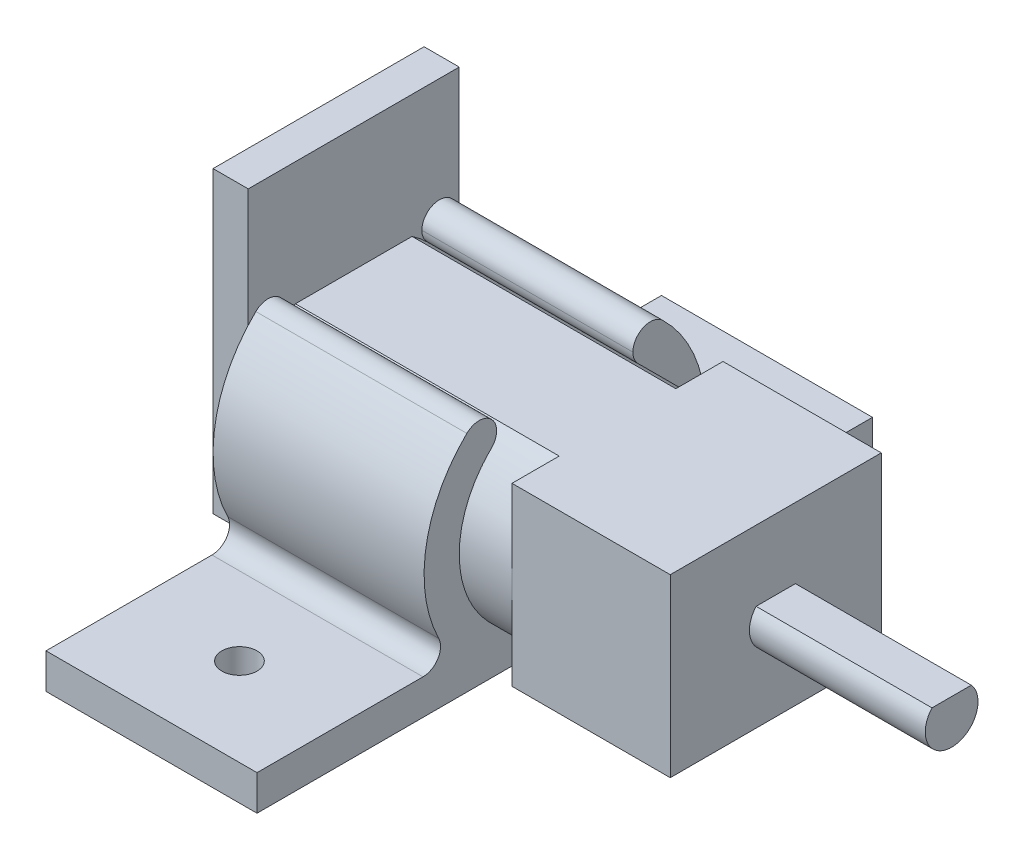
SolidWorks part; units mm, degrees
other "Motor Mount"
other "Motor"
ref_plane "Front Plane" through (0, 0, 0) normal (0, 0, 1) x (1, 0, 0)
ref_plane "Top Plane" through (0, 0, 0) normal (0, 1, 0) x (1, 0, 0)
ref_plane "Right Plane" through (0, 0, 0) normal (1, 0, 0) x (0, 0, -1)
sketch "Sketch1" plane through (0, 0, 0) normal (1, 0, 0) x (0, 0, -1)
  line L0 (0, 10) -> (12, 10)
  line L1 (0, 0) -> (12, 0)
  line L2 (0, 0) -> (0, 17)
  line L3 (0, 17) -> (12, 17)
  line L4 (12, 0) -> (12, 17)
  line L5 (6, 10) -> (6, 0) construction
  line L6 (4.882, 6) -> (7.118, 6)
  arc A0 (2.6834, 10) -> (2.6834, 0) centre (6, 5) ccw
  arc A1 (9.3166, 0) -> (9.3166, 10) centre (6, 5) ccw
  arc A2 (4.882, 6) -> (7.118, 6) centre (6, 5) ccw
  dimension "D4" = 3
  dimension "D5" = 1
  dimension "D1" = 12
  dimension "D2" = 17
  dimension "D3" = 10
extrude "Boss-Extrude1" add sketch "Sketch1" against normal blind 2 contours L0 L4 L3 L2 | A0 L0 L2 | L0 L5 L6 A2 L1 A1 | A1 L4 L0 | A1 L1 L4 | A0 L2 L1 | L5 L0 A0 L1 A2 L6 | L5 L6 A2 | L6 L5 A2 region at (0, 13.5, -6) region at (0, 8.8127, -0.7608) region at (0, 5.0095, -3.2137) region at (0, 1.1873, -0.7608) region at (0, 5.0095, -8.7863) region at (0, 8.8127, -11.2392) region at (0, 4.852, -6.662) region at (0, 4.852, -5.338) region at (0, 1.1873, -11.2392)
extrude "Boss-Extrude2" add sketch "Sketch1<3>" along normal blind 24 contours L0 L5 L6 A2 L1 A1 | A1 L4 L0 | A1 L1 L4 | L5 L0 A0 L1 A2 L6 | A0 L2 L1 | A0 L0 L2 | L5 L6 A2 | L6 L5 A2 region at (0, 8.8127, -0.7608) region at (0, 5.0095, -3.2137) region at (0, 1.1873, -0.7608) region at (0, 5.0095, -8.7863) region at (0, 8.8127, -11.2392) region at (0, 4.852, -6.662) region at (0, 4.852, -5.338) region at (0, 1.1873, -11.2392)
sketch "Sketch1<3>" plane through (0, 0, 0) normal (1, 0, 0) x (0, 0, -1) same geometry as "Sketch1"
extrude "Cut-Extrude1" cut sketch "Sketch1<4>" along normal blind 15 contours A1 L4 L0 | A0 L0 L2 | A0 L2 L1 | A1 L1 L4 region at (0, 8.8127, -0.7608) region at (0, 1.1873, -0.7608) region at (0, 8.8127, -11.2392) region at (0, 1.1873, -11.2392)
sketch "Sketch1<4>" plane through (0, 0, 0) normal (1, 0, 0) x (0, 0, -1) same geometry as "Sketch1"
extrude "Boss-Extrude3" add sketch "Sketch1<5>" along normal blind 34 contours L6 L5 A2 | L5 L6 A2 region at (0, 4.852, -6.662) region at (0, 4.852, -5.338)
sketch "Sketch1<5>" plane through (0, 0, 0) normal (1, 0, 0) x (0, 0, -1) same geometry as "Sketch1"
sketch "Sketch2" plane through (0, 0, 0) normal (1, 0, 0) x (0, 0, -1)
  line L2 (2.6834, 0) -> (9.3166, 0)
  line L5 (12.245, 0) -> (23.5, 0)
  line L6 (23.5, 0) -> (23.5, -2)
  line L8 (6, 10) -> (6, -2) construction
  line L10 (-11.5, 0) -> (-11.5, -2)
  line L11 (-0.245, 0) -> (-11.5, 0)
  line L12 (2.127, -2) -> (9.873, -2) construction
  line L13 (-11.5, -2) -> (23.5, -2)
  line L17 (2.127, 12) -> (9.873, 12) construction
  line L18 (2.6834, 10) -> (9.3166, 10) construction
  line L19 (0, 10) -> (12, 10) construction
  line L21 (2.127, 12) -> (2.127, 9.5826)
  line L22 (9.873, 12) -> (9.873, 9.5826)
  arc A0 (9.3166, 0) -> (12, 5) centre (6, 5) ccw construction
  arc A1 (12, 5) -> (9.3166, 10) centre (6, 5) ccw construction
  arc A2 (0, 5) -> (2.6834, 0) centre (6, 5) ccw construction
  arc A3 (2.6834, 10) -> (0, 5) centre (6, 5) ccw construction
  arc A4 (9.3166, 0) -> (12, 5) centre (6, 5) ccw
  arc A5 (12, 5) -> (9.3166, 10) centre (6, 5) ccw
  arc A6 (0, 5) -> (2.6834, 0) centre (6, 5) ccw
  arc A7 (2.6834, 10) -> (0, 5) centre (6, 5) ccw
  arc A8 (12.245, 0) -> (14, 5) centre (6, 5) ccw
  arc A9 (14, 5) -> (9.873, 12) centre (6, 5) ccw
  arc A10 (2.127, 12) -> (-2, 5) centre (6, 5) ccw
  arc A11 (-2, 5) -> (-0.245, 0) centre (6, 5) ccw
  arc A12 (-2, 5) -> (2.127, -2) centre (6, 5) ccw construction
  arc A13 (9.873, -2) -> (14, 5) centre (6, 5) ccw construction
  line M15 (0, 17) -> (0, 5)
  arc M16 (0, 5) -> (2.6834, 10) centre (6, 5) cw
  arc M18 (9.3166, 10) -> (12, 5) centre (6, 5) cw
  line M19 (12, 5) -> (12, 17)
  dimension "D2" = 35
  dimension "D3" = 2
  dimension "D1" = 2
extrude "Boss-Extrude4" add sketch "Sketch2" along normal blind 12 separate body contours L21 A10 M15 M16 | A10 A11 L11 L10 L13 L6 L5 A8 A9 A4 L2 A6 M19 M15 | A9 L22 M19 M18 region at (0, -0.371, -6) region at (0, 9.5704, -0.9554) region at (0, 9.5704, -11.0446)
sketch "Sketch3" plane through (0, -2, 0) normal (0, -1, 0) x (1, 0, 0)
  line L0 (6, 6.5) -> (6, 11.5) construction
  line L1 (12, 11.5) -> (0, 11.5) construction
  line L2 (12, -23.5) -> (0, -23.5) construction
  circle A0 centre (6, 6.5) radius 1
  circle A1 centre (6, -18.5) radius 1
  point P4 (6.5, 6.3362)
  dimension "D1" = 2
  dimension "D3" = 5
  dimension "D2" = 5
extrude "Cut-Extrude2" cut sketch "Sketch3" against normal blind 13
fillet "Fillet1" radius 1 6 edges at (6, 0, -12.245) (6, 0, 0.245) (6, 9.5826, -2.127) (6, 9.5826, -9.873) (6, 12, -9.873) (6, 12, -2.127)
